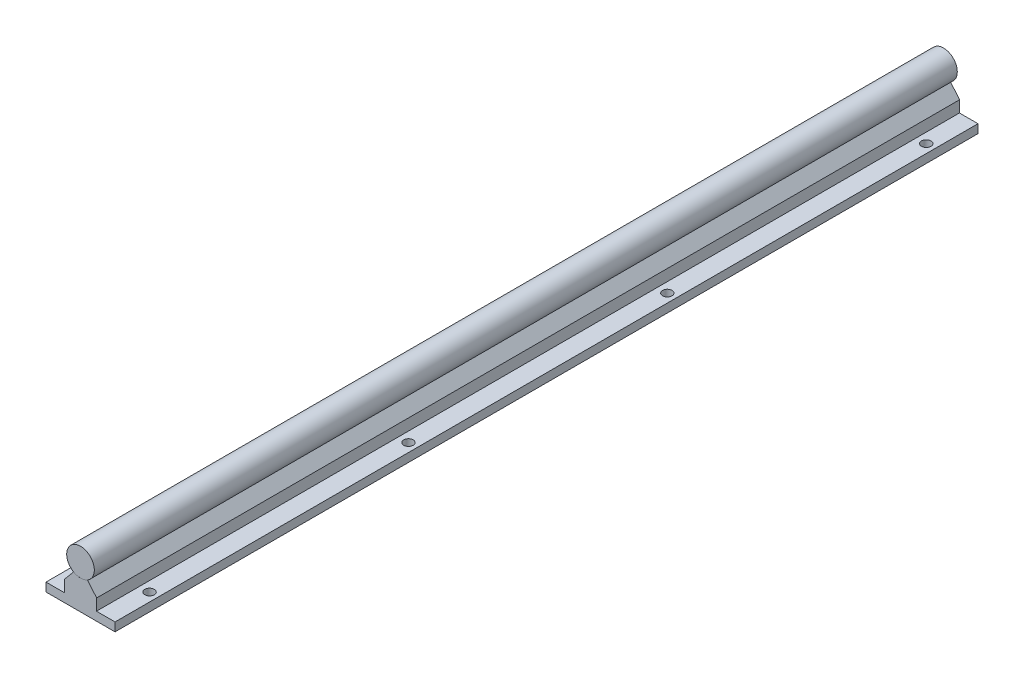
SolidWorks part; units mm, degrees
material "Chrome Stainless Steel"
ref_plane "Front" through (0, 0, 0) normal (0, 0, 1) x (1, 0, 0)
ref_plane "Top" through (0, 0, 0) normal (0, 1, 0) x (1, 0, 0)
ref_plane "Right" through (0, 0, 0) normal (1, 0, 0) x (0, 0, -1)
ref_axis "Axis1" through (-84.4107, 0, 0) along (1, 0, 0)
ref_axis "Axis2" through (0, 64.3378, 0) along (0, -1, 0)
ref_axis "Axis3" through (0, 0, -102.329) along (0, 0, 1)
sketch "Sketch1" plane through (0, 0, 0) normal (0, 0, 1) x (1, 0, 0)
  circle A0 centre (0, -1.8255) radius 8
  dimension "D1" = 16
extrude "Extrude1" add sketch "Sketch1" along normal blind 500
sketch "Sketch2" plane through (0, 0, 0) normal (0, 0, 1) x (1, 0, 0)
  line L0 (0, -8.7616) -> (0, -11.4511) construction
  line L1 (4, -8.7537) -> (9.3466, -15.1255)
  line L3 (9.25, -21.8255) -> (20, -21.8255)
  line L4 (20, -21.8255) -> (20, -26.8255)
  line L5 (20, -26.8255) -> (0, -26.8255)
  line L6 (0, -26.8255) -> (0, -9.8255)
  line L7 (0, -11.4511) -> (0, -13.4825) construction
  line L8 (9.3466, -15.1255) -> (9.25, -15.1255)
  line L9 (9.25, -15.1255) -> (9.25, -21.8255)
  arc A0 (0, -9.8255) -> (4, -8.7537) centre (0, -1.8255) ccw
  circle A1 centre (0, -1.8255) radius 8 construction
  circle A2 centre (0, -1.8255) radius 8 construction
  dimension "D1" = 4
  dimension "D2" = 40
  dimension "D3" = 5
  dimension "D4" = 11.7
  dimension "D5" = 9.25
  dimension "D6" = 25
  dimension "D7" = 20
extrude "Extrude3" add sketch "Sketch2" along normal blind 500 separate body
mirror "Mirror5" about plane through (0, -26.8255, 500) normal (1, 0, 0) of bodies 103
combine bodies "Combine1" operation type add bodies to combine 105 103
sketch "Sketch8" plane through (0, -26.8255, 0) normal (0, -1, 0) x (1, 0, 0)
  line L0 (0, -24.7558) -> (0, 504.6317) construction
  line L1 (38.9599, 475) -> (-38.5377, 475) construction
  line L7 (-20, 500) -> (-20, 0) construction
  circle A4 centre (-15, 475) radius 2.75
  circle A5 centre (15, 475) radius 2.75
  point P25 (-20, 250)
  dimension "D11" = 5.5
  dimension "D12" = 5.5
  dimension "D13" = 15
  dimension "D14" = 15
  dimension "D2" = 225
extrude "Cut-Extrude1" cut sketch "Sketch8" against normal up to next (5 mm away)
pattern_linear "LPattern1" count 4 spacing 150 along (0, 0, -1) of "Cut-Extrude1"
